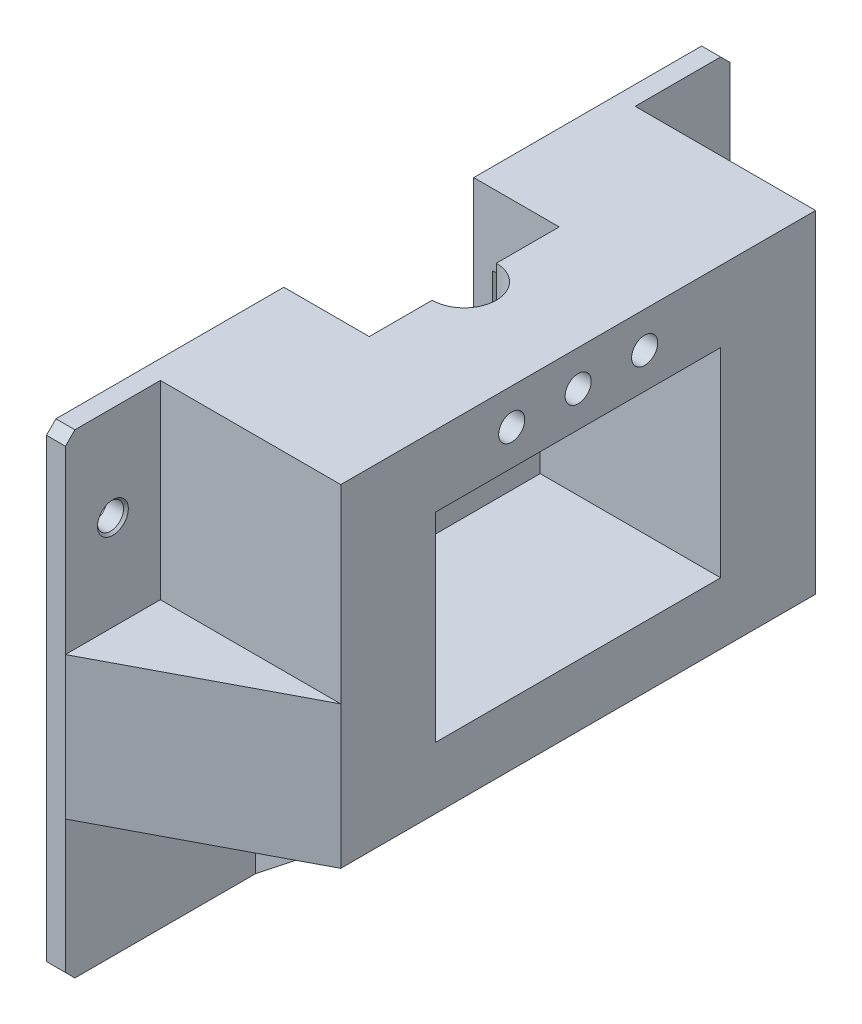
SolidWorks part; units mm, degrees
ref_plane "前视基准面" through (0, 0, 0) normal (0, 0, 1) x (1, 0, 0)
ref_plane "上视基准面" through (0, 0, 0) normal (0, 1, 0) x (1, 0, 0)
ref_plane "右视基准面" through (0, 0, 0) normal (1, 0, 0) x (0, 0, -1)
sketch "草图1" plane through (0, 0, 0) normal (1, 0, 0) x (0, 0, -1)
  line L1 (-70, 40) -> (70, 40)
  line L2 (-70, 40) -> (-70, -60)
  line L3 (-70, -60) -> (70, -60)
  line L4 (70, 40) -> (70, -60)
  dimension "D1" = 100
  dimension "D2" = 140
  dimension "D3" = 70
  dimension "D4" = 40
extrude "凸台-拉伸1" add sketch "草图1" along normal blind 4
sketch "草图9" plane through (4, 0, 0) normal (1, 0, 0) x (0, 0, -1)
  line L0 (70, -60) -> (70, 40) construction
  line L1 (-60, 20) -> (60, 20) construction
  line L2 (-60, 20) -> (-60, -40) construction
  line L3 (-60, -40) -> (60, -40) construction
  line L4 (60, 20) -> (60, -40) construction
  line L5 (70, 40) -> (-70, 40) construction
  circle A0 centre (-60, 20) radius 2.75
  circle A2 centre (60, 20) radius 2.75
  circle A4 centre (-45, -40) radius 2.75
  circle A5 centre (45, -40) radius 2.75
  dimension "D5" = 5.5
  dimension "D6" = 5.5
  dimension "D7" = 45
  dimension "D1" = 60
  dimension "D2" = 120
  dimension "D3" = 10
  dimension "D4" = 20
  dimension "D8" = 45
extrude "切除-拉伸3" cut sketch "草图9" against normal blind 8
chamfer "倒角2" distance 2 angle 45 4 edges at (2, -60, -70) (2, 40, -70) (2, 40, 70) (2, -60, 70)
sketch "草图11" plane through (4, 0, 0) normal (1, 0, 0) x (0, 0, -1)
  line L0 (68, 40) -> (-68, 40) construction
  line L1 (-20, 40) -> (20, 40)
  line L2 (-20, 40) -> (-20, -10)
  line L3 (-20, -10) -> (20, -10)
  line L4 (20, 40) -> (20, -10)
  dimension "D1" = 20
  dimension "D2" = 20
  dimension "D3" = 10
extrude "切除-拉伸5" cut sketch "草图11" against normal blind 5
sketch "草图12" plane through (4, 0, 0) normal (1, 0, 0) x (0, 0, -1)
  line L1 (-20, 40) -> (-30, 40)
  line L2 (-20, 40) -> (-20, 25)
  line L3 (-20, 25) -> (-30, 25)
  line L4 (-30, 40) -> (-30, 25)
  line L5 (20, 40) -> (30, 40)
  line L6 (20, 40) -> (20, 25)
  line L7 (20, 25) -> (30, 25)
  line L8 (30, 40) -> (30, 25)
  dimension "D1" = 10
  dimension "D2" = 10
  dimension "D3" = 15
  dimension "D4" = 15
extrude "凸台-拉伸2" add sketch "草图12" along normal blind 14
sketch "草图13" plane through (18, 0, 0) normal (1, 0, 0) x (0, 0, -1)
  line L1 (-30, 40) -> (30, 40)
  line L2 (-30, 40) -> (-30, 25)
  line L3 (-30, 25) -> (30, 25)
  line L4 (30, 40) -> (30, 25)
extrude "凸台-拉伸3" add sketch "草图13" along normal blind 14
sketch "草图14" plane through (0, 0, 30) normal (0, 0, 1) x (1, 0, 0)
  line L0 (4, 40) -> (4, -30)
  line L3 (32, -30) -> (32, 40)
  line L4 (32, 40) -> (4, 40)
  line L6 (32, -30) -> (4, -30)
  line L7 (4, 38) -> (4, -58) construction
  dimension "D1" = 70
extrude "凸台-拉伸4" add sketch "草图14" along normal blind 20
sketch "草图15" plane through (0, 0, -30) normal (0, 0, -1) x (-1, 0, 0)
  line L4 (-4, 40) -> (-32, 40)
  line L5 (-4, -30) -> (-4, 40)
  line L6 (-32, -30) -> (-4, -30)
  line L7 (-32, 40) -> (-32, -30)
  line L8 (-4, 40) -> (-32, 40)
  line L9 (-4, -30) -> (-4, 40)
  line L11 (-32, 40) -> (-32, -30)
  line L12 (-32, -30) -> (-4, -30)
  dimension "D1" = 0
extrude "凸台-拉伸5" add sketch "草图15" along normal blind 20
sketch "草图16" plane through (0, 40, 0) normal (0, 1, 0) x (1, 0, 0)
  line L0 (18, 20) -> (18, -20) construction
  circle A0 centre (18, 0) radius 6.75
  dimension "D1" = 13.5
extrude "切除-拉伸6" cut sketch "草图16" against normal blind 20
sketch "草图17" plane through (32, 0, 0) normal (1, 0, 0) x (0, 0, -1)
  line L6 (50, 40) -> (-50, 40)
  line L7 (-50, 40) -> (-50, -30)
  line L8 (-50, -30) -> (-30, -30)
  line L9 (-30, 25) -> (30, 25)
  line L10 (30, -30) -> (50, -30)
  line L11 (50, -30) -> (50, 40)
  line L12 (50, 40) -> (-50, 40)
  line L13 (-50, 40) -> (-50, -30)
  line L15 (-30, 25) -> (30, 25)
  line L16 (30, -30) -> (50, -30)
  line L17 (50, -30) -> (50, 40)
  line L20 (-50, -30) -> (-30, -30)
  line L21 (-30, -30) -> (-30, 25)
  line L22 (-30, -30) -> (-30, 25)
  line L23 (30, 25) -> (30, -30)
  line L24 (30, 25) -> (30, -30)
  dimension "D1" = 0
extrude "凸台-拉伸6" add sketch "草图17" along normal blind 10
sketch "草图18" plane through (18, 0, 0) normal (-1, 0, 0) x (0, 0, 1)
  line L0 (6.75, 40) -> (20, 40) construction
  line L1 (-20, 40) -> (-6.75, 40) construction
  circle A0 centre (14, 32.5) radius 2.75
  circle A1 centre (-14, 32.5) radius 2.75
  dimension "D1" = 5.5
  dimension "D2" = 5.5
  dimension "D3" = 28
  dimension "D4" = 14
  dimension "D5" = 7.5
  dimension "D6" = 7.5
extrude "切除-拉伸7" cut sketch "草图18" against normal through all
sketch "草图19" plane through (42, 0, 0) normal (1, 0, 0) x (0, 0, -1)
  circle A0 centre (0, 32.5) radius 2.75
  dimension "D1" = 5.5
  dimension "D2" = 32.5
extrude "切除-拉伸8" cut sketch "草图19" against normal blind 100
chamfer "倒角3" distance 0.5 angle 45 4 edges at (4, -40, 42.25) (4, -40, -47.75) (4, 20, -62.75) (4, 20, 57.25)
sketch "草图20" plane through (0, 0, 50) normal (0, 0, 1) x (1, 0, 0)
  line L0 (42, 25) -> (4, -30)
  line L1 (4, -30) -> (32, 25)
  line L2 (32, 25) -> (42, 25)
  line L5 (42, 40) -> (42, -30) construction
  point P4 (32, 25)
  point P7 (0, 0)
  dimension "D1" = 10
  dimension "D2" = 32
  dimension "D3" = 25
  dimension "D4" = 30
  dimension "D5" = 38
extrude "凸台-拉伸7" add sketch "草图20" against normal blind 20
sketch "草图21" plane through (0, 0, -50) normal (0, 0, -1) x (-1, 0, 0)
  line L0 (-42, 25) -> (-4, -30)
  line L1 (-4, -30) -> (-32, 25)
  line L2 (-32, 25) -> (-42, 25)
  point P4 (0, 0)
  dimension "D1" = 10
  dimension "D2" = 32
  dimension "D3" = 25
extrude "凸台-拉伸8" add sketch "草图21" against normal blind 20
sketch "草图22" plane through (0, 0, -30) normal (0, 0, 1) x (1, 0, 0)
  line L0 (42, -17) -> (4, -17)
  line L1 (42, 25) -> (42, -30) construction
  line L2 (4, -30) -> (4, 25) construction
  line L3 (4, -17) -> (4, -60)
  line L5 (42, 25) -> (4, 25) construction
  line L6 (42, -17) -> (42, -30)
  line L7 (42, -30) -> (4, -60)
  dimension "D1" = 42
extrude "凸台-拉伸9" add sketch "草图22" along normal up to surface (60 mm away) up to face at (23, -2.5, 30)
sketch "草图23" plane through (0, -30, 0) normal (0, -1, 0) x (1, 0, 0)
  line L0 (42, 50) -> (4, 70)
  line L1 (4, 70) -> (4, 50)
  line L2 (4, 50) -> (42, 50)
extrude "凸台-拉伸10" add sketch "草图23" against normal blind 30
mirror "镜向1" about plane through (0, 0, 0) normal (0, 0, 1) of "凸台-拉伸10"
